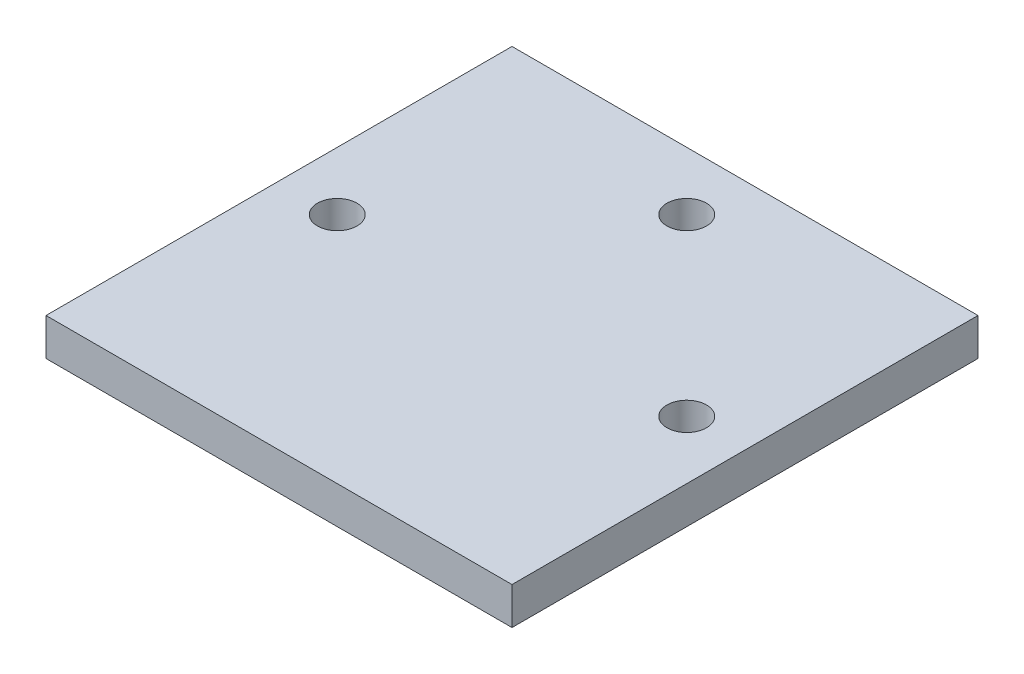
SolidWorks part; units mm, degrees
material "AISI 1020"
ref_plane "Спереди" through (0, 0, 0) normal (0, 0, 1) x (1, 0, 0)
ref_plane "Сверху" through (0, 0, 0) normal (0, 1, 0) x (1, 0, 0)
ref_plane "Справа" through (0, 0, 0) normal (1, 0, 0) x (0, 0, -1)
sketch "Эскиз1" plane through (0, 0, 0) normal (0, 1, 0) x (1, 0, 0)
  line L1 (-100, -100) -> (100, -100)
  line L2 (-100, -100) -> (-100, 100)
  line L3 (-100, 100) -> (100, 100)
  line L4 (100, -100) -> (100, 100)
  line L5 (-100, -100) -> (100, 100) construction
  line L6 (-100, 100) -> (100, -100) construction
  line L7 (-75, -75) -> (75, -75) construction
  line L8 (-75, -75) -> (-75, 75) construction
  line L9 (-75, 75) -> (75, 75) construction
  line L10 (75, -75) -> (75, 75) construction
  circle A0 centre (0, 75) radius 8.5
  circle A1 centre (-75, 0) radius 8.5
  circle A2 centre (75, 0) radius 8.5
  point P0 (0, 0)
  dimension "D2" = 17
  dimension "D1" = 200
  dimension "D3" = 150
base flange "Базовая кромка1" sketch "Эскиз1" thickness 16 reverse thickness direction no parameters "D1"=0.75
sketch "Сгиб-Линии1" plane through (0, 0, 0) normal (0, 1, 0) x (1, 0, 0)
sketch "Граничная рамка1" plane through (0, 0, 0) normal (0, 1, 0) x (1, 0, 0)
sheet metal parameters "Листовой металл3" thickness 16 parameters "D1"=0.75
flat pattern "Развертка3" [suppressed]
sketch "Сгиб-Линии2" plane through (0, 0, 0) normal (0, 1, 0) x (1, 0, 0)
sketch "Граничная рамка2" [suppressed] plane through (0, 0, 0) normal (0, 1, 0) x (1, 0, 0)
